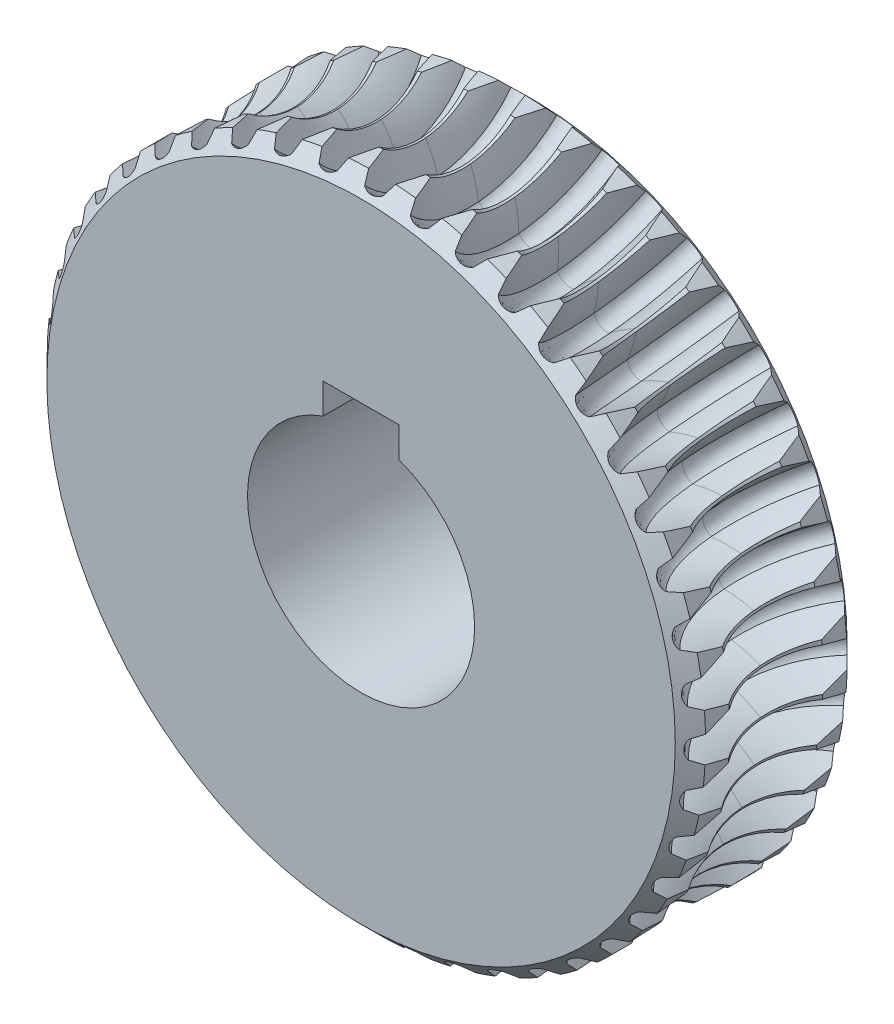
SolidWorks part; units mm, degrees
note: The reader was unsure of these and kept them because the rebuilt part matched: shared geometry of "Croquis4<2>".
ref_plane "Alzado" through (0, 0, 0) normal (0, 0, 1) x (1, 0, 0)
ref_plane "Planta" through (0, 0, 0) normal (0, 1, 0) x (1, 0, 0)
ref_plane "Vista lateral" through (0, 0, 0) normal (1, 0, 0) x (0, 0, -1)
sketch "Croquis1" plane through (0, 0, 0) normal (0, 0, 1) x (1, 0, 0)
  line L0 (0, 0) -> (0, 24.9347) construction
  line L2 (-5, 18.1421) -> (5, 18.1421)
  line L3 (-5, 18.1421) -> (-5, 14.1421)
  line L5 (5, 18.1421) -> (5, 14.1421)
  circle A0 centre (0, 0) radius 43.5
  arc A1 (-5, 14.1421) -> (5, 14.1421) centre (0, 0) ccw
  dimension "D1" = 87
  dimension "D2" = 30
  dimension "D3" = 10
  dimension "D4" = 4
extrude "Saliente-Extruir1" add sketch "Croquis1" along normal mid plane 22.7
chamfer "Chaflán1" distance 2 angle 45 2 edges at (43.5, 0, -11.35) (43.5, 0, 11.35)
sketch "Croquis2" plane through (0, 0, 0) normal (1, 0, 0) x (0, 0, -1)
  line L0 (0, 0) -> (0, -52) construction
  line L1 (0, 0) -> (60.5738, 0) construction
  circle A0 centre (0, -52) radius 10.5
  dimension "D2" = 21
  dimension "D1" = 52
revolve "Cortar-Revolución1" cut sketch "Croquis2" angle 360 about L1
sketch "Croquis3" plane through (0, 0, 0) normal (1, 0, 0) x (0, 0, -1)
  circle A1 centre (0, -52) radius 10.5
  circle A2 centre (0, -52) radius 10.5
  dimension "D1" = 0
curve "Hélice/Espiral1" pitch 6 height 1.5 turns 0.25
sketch "Croquis4" plane through (0, 0, 0) normal (0, 0, 1) x (1, 0, 0)
  line L0 (0, 0) -> (0, -48.7834) construction
  line L1 (-3.45, -44.94) -> (3.45, -44.94)
  line L2 (-3.45, -44.94) -> (-3.45, -42.44)
  line L3 (3.45, -44.94) -> (3.45, -42.44)
  arc A0 (-1.2018, -37.79) -> (1.2018, -37.79) centre (0, -39.13) cw
  arc A1 (-3.45, -42.44) -> (-1.2018, -37.79) centre (-18.3636, -32.3611) ccw
  arc A2 (3.45, -42.44) -> (1.2018, -37.79) centre (18.3636, -32.3611) cw
  point P12 (-3.0641, -46.2751)
  dimension "D2" = 1.8
  dimension "D4" = 18
  dimension "D1" = 39.13
  dimension "D3" = 6.9
  dimension "D5" = 4.65
  dimension "D6" = 1.34
  dimension "D7" = 2.5
sweep "Cortar-Barrer1" cut profiles "Croquis4" path "Hélice/Espiral1" align with end faces yes
sketch "Croquis8" plane through (0, 0, 0) normal (1, 0, 0) x (0, 0, -1)
  circle A1 centre (0, -52) radius 10.5
  circle A2 centre (0, -52) radius 10.5
  dimension "D1" = 0
curve "Hélice/Espiral2" pitch 6 height 1.5 turns 0.25
sweep "Cortar-Barrer2" cut profiles "Croquis4<2>" path "Hélice/Espiral2"
sketch "Croquis4<2>" plane through (0, 0, 0) normal (0, 0, 1) x (1, 0, 0) same geometry as "Croquis4"
pattern_circular "MatrizC1" count 44 over 360 about axis through (0, 0, 11.35) along (0, 0, -1) of "Cortar-Barrer1", "Cortar-Barrer2" reverse direction yes
